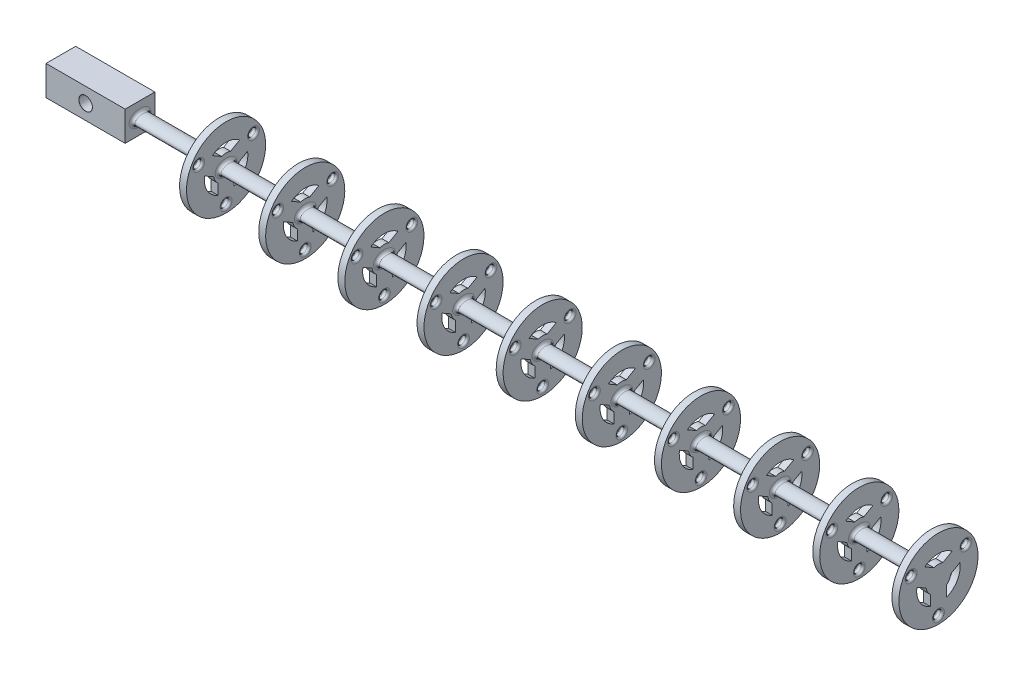
SolidWorks part; units mm, degrees
ref_plane "Front Plane" through (0, 0, 0) normal (0, 0, 1) x (1, 0, 0)
ref_plane "Top Plane" through (0, 0, 0) normal (0, 1, 0) x (1, 0, 0)
ref_plane "Right Plane" through (0, 0, 0) normal (1, 0, 0) x (0, 0, -1)
sketch "Sketch21" plane through (0, 0, 0) normal (1, 0, 0) x (0, 0, -1)
  ellipse E0 centre (0, 0) end of major axis (2, 0) minor radius 1.25
  point P1 (0, 0)
  dimension "D1" = 1.25
  dimension "D2" = 2
extrude "Boss-Extrude6" add sketch "Sketch21" along normal blind 200
sketch "Sketch3" plane through (0, 0, 0) normal (0, 0, 1) x (1, 0, 0)
  line L0 (20, 0) -> (20, 10)
  line L1 (20, 10) -> (21.75, 10)
  line L2 (21.75, 10) -> (21.75, 0)
  line L3 (21.75, 0) -> (20, 0)
  line L4 (0, -11) -> (0, 11) construction
  dimension "D1" = 1.75
  dimension "D2" = 10
  dimension "D3" = 20
revolve "Revolve2" add sketch "Sketch3" angle 360 about L3
sketch "Sketch5" plane through (21.75, 0, 0) normal (1, 0, 0) x (0, 0, -1)
  line L0 (0, -8) -> (0, 0) construction
  line L1 (0, 0) -> (6.9282, 4) construction
  line L2 (-6.9282, 4) -> (0, 0) construction
  line L3 (0, 11) -> (0, -11) construction
  line L4 (-3.4371, 4.2938) -> (-1.1282, 2.9608)
  line L5 (1.1282, 2.9608) -> (3.4371, 4.2938)
  line L6 (2, -2.4574) -> (2, -5.1235)
  line L7 (5.4371, 0.8297) -> (3.1282, -0.5033)
  line L8 (-3.1282, -0.5033) -> (-5.4371, 0.8297)
  line L9 (-2, -5.1235) -> (-2, -2.4574)
  circle A0 centre (0, -8) radius 1
  circle A1 centre (6.9282, 4) radius 1
  circle A2 centre (-6.9282, 4) radius 1
  arc A3 (-3.4371, 4.2938) -> (3.4371, 4.2938) centre (0, 0) cw
  circle A6 centre (0, 0) radius 10 construction
  arc A8 (-1.1282, 2.9608) -> (1.1282, 2.9608) centre (0, 0) cw
  arc A10 (5.4371, 0.8297) -> (2, -5.1235) centre (0, 0) cw
  arc A11 (3.1282, -0.5033) -> (2, -2.4574) centre (0, 0) cw
  arc A12 (-2, -5.1235) -> (-5.4371, 0.8297) centre (0, 0) cw
  arc A13 (-2, -2.4574) -> (-3.1282, -0.5033) centre (0, 0) cw
  point P29 (0, 0)
  dimension "D2" = 2
  dimension "D5" = 3.1684
  dimension "D1" = 8
  dimension "D3" = 120
  dimension "D4" = 120
  dimension "D6" = 2
  dimension "D7" = 4.5
  dimension "D8" = 3
extrude "Cut-Extrude1" cut sketch "Sketch5" against normal up to next
fillet "Fillet1" radius 0.5 6 edges at (20, 3, -6.9282) (20, -9, 0) (21.75, -7, 0) (21.75, 5, -6.9282) (20, 3, 6.9282) (21.75, 5, 6.9282)
pattern_linear "LPattern1" count 10 spacing 20 along (1, 0, 0) of "Revolve2", "Cut-Extrude1", "Fillet1"
sketch "Sketch16" plane through (0, 0, 0) normal (1, 0, 0) x (0, 0, -1)
  line L1 (-3.75, -3.75) -> (3.75, -3.75)
  line L2 (-3.75, -3.75) -> (-3.75, 3.75)
  line L3 (-3.75, 3.75) -> (3.75, 3.75)
  line L4 (3.75, -3.75) -> (3.75, 3.75)
  line L5 (-3.75, -3.75) -> (3.75, 3.75) construction
  line L6 (-3.75, 3.75) -> (3.75, -3.75) construction
  point P0 (0, 0)
  dimension "D1" = 7.5
extrude "Boss-Extrude1" add sketch "Sketch16" against normal blind 20
sketch "Sketch19" plane through (0, 0, 3.75) normal (0, 0, 1) x (1, 0, 0)
  line L1 (-20, 3.75) -> (0, 3.75) construction
  line L2 (-20, 3.75) -> (-20, -3.75) construction
  point P0 (-10, 0)
  point P7 (-10, 3.75)
  point P10 (-20, 0)
hole_wizard "M3 Clearance Hole1" positions "Sketch19" profile "Sketch18" hole size "M3" standard "ANSI Metric" end condition through all
sketch "Sketch18" plane through (-10, 0, 3.75) normal (1, 0, 0) x (0, -1, 0)
  line L0 (0, 0) -> (0, 13.75)
  line L1 (0, 13.75) -> (1.7, 13.75)
  line L2 (1.7, 13.75) -> (1.7, 0.025)
  line L3 (1.7, 0.025) -> (1.725, 0)
  line L5 (1.725, 0) -> (0, 0)
  line L6 (-1.7, 0.025) -> (-1.725, 0) construction
  line L11 (0, -6.35) -> (0, 107.95) construction
  dimension "Thru Hole Dia." = 3.4
  dimension "Thru Hole Depth" = 13.75
  dimension "Near C'Sink Dia." = 3.45
  dimension "Near C'Sink Angle" = 90
fillet "Fillet2" radius 0.75 20 edges at (200, 0, -2) (181.75, 0, -2) (180, 0, -2) (161.75, 0, -2) (160, 0, -2) (141.75, 0, -2) (140, 0, -2) (121.75, 0, -2) (120, 0, -2) (101.75, 0, -2) (100, 0, -2) (81.75, 0, -2) (80, 0, -2) (61.75, 0, -2) (60, 0, -2) (41.75, 0, -2) (40, 0, -2) (21.75, 0, -2) (20, 0, -2) (0, 0, -2)
equation "\"R_initial\"= 1.75"
equation "\"D1@Sketch2\"=\"R_initial\""
equation "\"R_distal\"= 1.0"
equation "\"D3@Sketch2\"=\"R_distal\""
equation "\"L\"=200"
equation "\"D2@Sketch2\"=\"L\""
equation "\"disk_thickness\"= 1.75"
equation "\"D1@Sketch3\"=\"disk_thickness\""
equation "\"disk_radius\"= 10"
equation "\"D2@Sketch3\"=\"disk_radius\""
equation "\"disk_spacing_initial\"= 20"
equation "\"D3@Sketch3\"=\"disk_spacing_initial\""
equation "\"tendon_routing_radius\"= 8"
equation "\"D1@Sketch5\"=\"tendon_routing_radius\""
equation "\"tendon_routing_hole_radius\"=2"
equation "\"D2@Sketch5\"=\"tendon_routing_hole_radius\""
equation "\"tendon_routing_hole_fillet\"=0.5"
equation "\"D1@Fillet1\"=\"tendon_routing_hole_fillet\""
equation "\"inter_disk_spacing\"= 20"
equation "\"D3@LPattern1\"=\"inter_disk_spacing\""
equation "\"num_disk\"= 10"
equation "\"D1@LPattern1\"=\"num_disk\""
